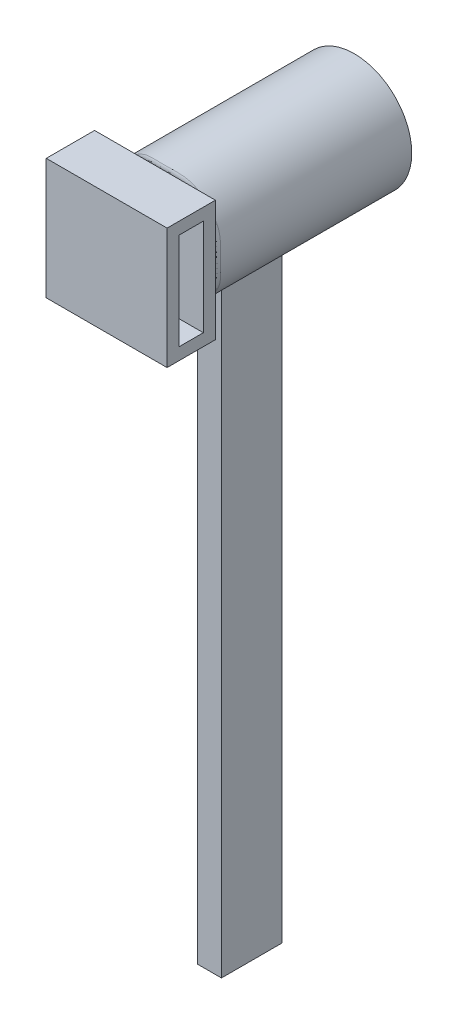
SolidWorks part; units mm, degrees
ref_plane "Front Plane" through (0, 0, 0) normal (0, 0, 1) x (1, 0, 0)
ref_plane "Top Plane" through (0, 0, 0) normal (0, 1, 0) x (1, 0, 0)
ref_plane "Right Plane" through (0, 0, 0) normal (1, 0, 0) x (0, 0, -1)
sketch "Sketch2" plane through (0, 0, 0) normal (0, 0, 1) x (1, 0, 0)
  circle A4 centre (0, 0) radius 4.75
  point P3 (25, 0)
  dimension "D1" = 9.5
ref_plane "Plane1" through (0, 0, 16.5) normal (0, 0, 1) x (1, 0, 0)
sketch "Sketch3" plane through (0, 0, 16.5) normal (0, 0, 1) x (1, 0, 0)
  line L0 (-5, 5) -> (5, 5)
  line L1 (-5, 5) -> (-5, -5)
  line L2 (-5, -5) -> (5, -5)
  line L3 (5, 5) -> (5, -5)
  circle A0 centre (0, 0) radius 4.75
  point P3 (0, 5)
  point P9 (5, 0)
  dimension "D1" = 9.5
  dimension "D2" = 10
loft "Loft1" add profiles "Sketch2", "Sketch3" connector at (0.4143, 4.7319, 0) connector at (0.1582, 4.7474, 16.5)
sketch "Sketch4" plane through (0, 0, 0) normal (0, 1, 0) x (1, 0, 0)
  line L1 (1, -12) -> (-1, -12)
  line L2 (1, -12) -> (1, -7)
  line L3 (1, -7) -> (-1, -7)
  line L4 (-1, -12) -> (-1, -7)
  line L7 (-4.75, 0) -> (-4.75, -16.5) construction
  line L8 (4.75, 0) -> (-4.75, 0) construction
  dimension "D1" = 7
  dimension "D2" = 3.75
  dimension "D3" = 5
  dimension "D4" = 2
extrude "Boss-Extrude1" add sketch "Sketch4" against normal blind 55
extrude "Boss-Extrude4" add sketch "Sketch3<7>" along normal blind 4 contours A0 L3 L0 L1 | A0 L1 L2 L3 | A0 | A0 L0 L1 | A0 L2 L3 region at (0, 4.8586, 16.5) region at (0, 0, 16.5)
sketch "Sketch3<7>" plane through (0, 0, 16.5) normal (0, 0, 1) x (1, 0, 0) same geometry as "Sketch3"
sketch "Sketch8" plane through (5, 0, 0) normal (1, 0, 0) x (0, 0, -1)
  line L0 (-20.5, 5) -> (-20.5, -5) construction
  line L1 (-19.5, 4) -> (-17.5, 4)
  line L2 (-19.5, 4) -> (-19.5, -4)
  line L3 (-19.5, -4) -> (-17.5, -4)
  line L4 (-17.5, 4) -> (-17.5, -4)
  line L5 (-20.5, 5) -> (-16.5, 5) construction
  point P4 (-19.5, 0)
  point P7 (-20.5, 0)
  point P8 (-18.5, 4)
  point P11 (-18.5, 5)
  dimension "D1" = 2
  dimension "D2" = 8
extrude "Cut-Extrude2" cut sketch "Sketch8" against normal through all both and the other way through all
fillet "Fillet1" radius 1 1 edges at (4.75, 0, 16.5)
fillet "Fillet2" radius 1 4 edges at (0, -4.75, 12) (-1, -4.6435, 9.5) (0, -4.75, 7) (1, -4.6435, 9.5)
